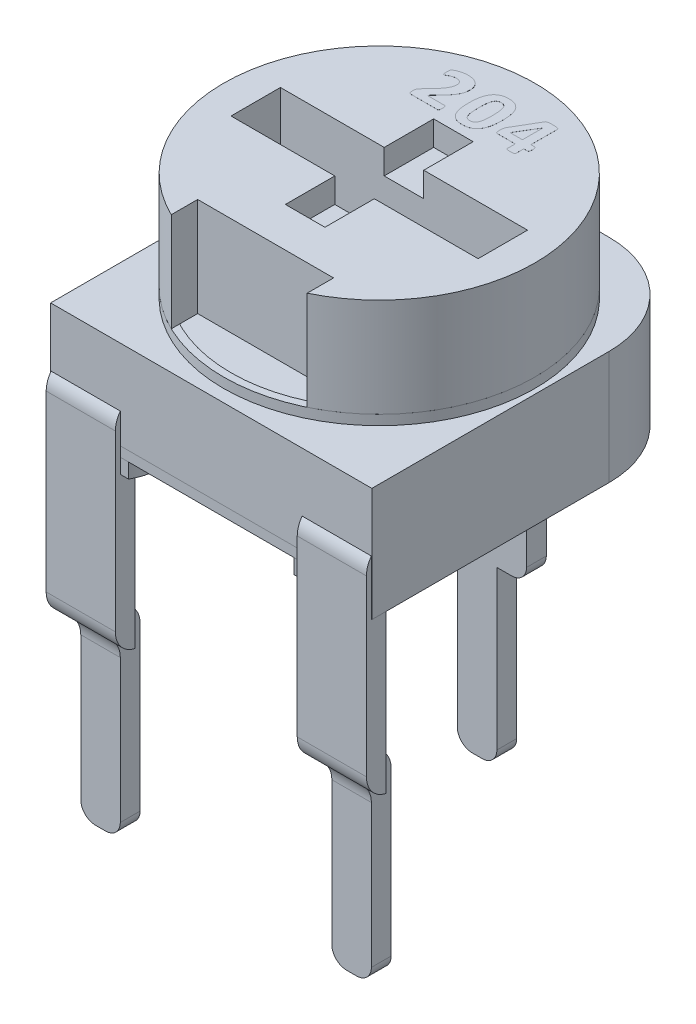
SolidWorks part; units mm, degrees
material "ABS"
ref_plane "Front Plane" through (0, 0, 0) normal (0, 0, 1) x (1, 0, 0)
ref_plane "Top Plane" through (0, 0, 0) normal (0, 1, 0) x (1, 0, 0)
ref_plane "Right Plane" through (0, 0, 0) normal (1, 0, 0) x (0, 0, -1)
sketch "Sketch1" plane through (0, 0, 0) normal (0, 1, 0) x (1, 0, 0)
  line L0 (0, 3.15) -> (0, -3.15) construction
  line L1 (0, 3.15) -> (0, 3.4) construction
  line L2 (0, -3.15) -> (0, -3.4) construction
  line L3 (-3.15, 0) -> (3.15, 0) construction
  line L4 (3.15, 0) -> (3.25, 0) construction
  line L5 (-3.15, 0) -> (-3.25, 0) construction
  line L6 (-3.25, -3.4) -> (3.25, -3.4)
  line L7 (-3.25, -3.4) -> (-3.25, 3.4)
  line L8 (-3.25, 3.4) -> (3.25, 3.4)
  line L9 (3.25, 3.4) -> (3.25, -3.4)
  circle A0 centre (0, 0) radius 3.15 construction
  dimension "D1" = 6.3
  dimension "D2" = 6.8
  dimension "D3" = 6.5
extrude "Boss-Extrude1" add sketch "Sketch1" along normal blind 2.3
sketch "Sketch2" plane through (0, 2.3, 0) normal (0, 1, 0) x (1, 0, 0)
  circle A0 centre (0, 0) radius 3.15 construction
  circle A1 centre (0, 0) radius 3.15
extrude "Boss-Extrude2" add sketch "Sketch2" along normal blind 0.2
fillet "Fillet1" radius 2 2 edges at (3.25, 1.15, -3.4) (-3.25, 1.15, -3.4)
sketch "Sketch3" plane through (0, 0, 0) normal (0, -1, 0) x (1, 0, 0)
  line L0 (0, 0) -> (0, -2.5) construction
  line L1 (-1.75, -2.5) -> (1.75, -2.5)
  line L6 (-2.25, -2) -> (-2.25, 2)
  line L7 (2.25, -2) -> (2.25, 2)
  line L8 (-2.25, 2) -> (-3, 2)
  line L9 (-3, 2) -> (-3, 3.4)
  line L10 (-3.25, 3.4) -> (3.25, 3.4) construction
  line L11 (2.25, 2) -> (3, 2)
  line L12 (3, 2) -> (3, 3.4)
  line L13 (3, 3.4) -> (-3, 3.4)
  line L14 (0, 0) -> (0, 3.4) construction
  arc A0 (-1.75, -2.5) -> (-2.25, -2) centre (-1.75, -2) cw
  arc A1 (1.75, -2.5) -> (2.25, -2) centre (1.75, -2) ccw
  point P20 (2.25, -2.5)
  dimension "D6" = 0.5
  dimension "D1" = 4.5
  dimension "D2" = 2.5
  dimension "D3" = 4.5
  dimension "D4" = 1.4
  dimension "D5" = 6
extrude "Cut-Extrude1" cut sketch "Sketch3" against normal blind 0.5
sketch "Sketch4" plane through (0, 0.5, 0) normal (0, -1, 0) x (1, 0, 0)
  line L8 (-3, 2) -> (-2.25, 2)
  line L9 (-2.25, 2) -> (-2.25, -2)
  line L10 (-1.75, -2.5) -> (1.75, -2.5)
  line L11 (2.25, -2) -> (2.25, 2)
  line L12 (2.25, 2) -> (3, 2)
  line L13 (3, 2) -> (3, 3.4)
  line L14 (3, 3.4) -> (-3, 3.4)
  line L15 (-3, 3.4) -> (-3, 2)
  line L16 (-3, 2) -> (-2.25, 2)
  line L17 (-2.25, 2) -> (-2.25, -2)
  line L18 (-1.75, -2.5) -> (1.75, -2.5)
  line L19 (2.25, -2) -> (2.25, 2)
  line L20 (2.25, 2) -> (3, 2)
  line L21 (3, 2) -> (3, 3.4)
  line L22 (3, 3.4) -> (-3, 3.4)
  line L23 (-3, 3.4) -> (-3, 2)
  arc A2 (-2.25, -2) -> (-1.75, -2.5) centre (-1.75, -2) ccw
  arc A3 (1.75, -2.5) -> (2.25, -2) centre (1.75, -2) ccw
  arc A4 (-2.25, -2) -> (-1.75, -2.5) centre (-1.75, -2) ccw
  arc A5 (1.75, -2.5) -> (2.25, -2) centre (1.75, -2) ccw
  dimension "D1" = 0
extrude "Boss-Extrude3" add sketch "Sketch4" along normal blind 0.2 separate body
sketch "Sketch5" plane through (0, 0.3, 0) normal (0, -1, 0) x (1, 0, 0)
  line L0 (0, 3.4) -> (0, 2.9) construction
  line L1 (3, 3.4) -> (-3, 3.4) construction
  line L2 (0, 2.9) -> (0, -2.18) construction
  line L3 (-2.54, 2.9) -> (2.54, 2.9) construction
  circle A0 centre (2.54, 2.9) radius 1
  circle A1 centre (-2.54, 2.9) radius 1
  circle A2 centre (0, -2.18) radius 1
  dimension "D2" = 5.08
  dimension "D4" = 2
  dimension "D1" = 0.5
  dimension "D3" = 5.08
extrude "Boss-Extrude4" add sketch "Sketch5" along normal up to surface (0.3 mm away) up to face at (0, 0, 0.1228)
sketch "Sketch6" plane through (0, 0.3, 0) normal (0, 1, 0) x (1, 0, 0)
  line L0 (-3.25, -3.4) -> (-3.25, -1)
  line L1 (-3.25, 1.4) -> (-3.25, -3.4) construction
  line L2 (-3.25, -1) -> (-4.35, -1)
  line L3 (-4.35, -1) -> (-4.35, -4.5)
  line L4 (-4.35, -4.5) -> (4.35, -4.5)
  line L5 (4.35, -4.5) -> (4.35, -1)
  line L6 (4.35, -1) -> (3.25, -1)
  line L7 (3.25, -3.4) -> (3.25, 1.4) construction
  line L8 (-3.25, -3.4) -> (3.25, -3.4)
  line L9 (3.25, -3.4) -> (3.25, -1)
  line L10 (0, 0) -> (0, -3.4) construction
  line L11 (0, -3.4) -> (0, -4.5) construction
  dimension "D1" = 3.5
extrude "Cut-Extrude2" cut sketch "Sketch6" against normal up to surface (0.3 mm away) up to face at (0, 0, -0.817)
sketch "Sketch8" plane through (0, 0.3, 0) normal (0, -1, 0) x (1, 0, 0)
  line L1 (-0.4, -1.98) -> (0.4, -1.98)
  line L2 (-0.4, -1.98) -> (-0.4, -2.38)
  line L3 (-0.4, -2.38) -> (0.4, -2.38)
  line L4 (0.4, -1.98) -> (0.4, -2.38)
  line L5 (-0.4, -1.98) -> (0.4, -2.38) construction
  line L6 (-0.4, -2.38) -> (0.4, -1.98) construction
  line L7 (-2.94, 3.1) -> (-2.14, 3.1)
  line L8 (-2.94, 3.1) -> (-2.94, 2.7)
  line L9 (-2.94, 2.7) -> (-2.14, 2.7)
  line L10 (-2.14, 3.1) -> (-2.14, 2.7)
  line L11 (-2.94, 3.1) -> (-2.14, 2.7) construction
  line L12 (-2.94, 2.7) -> (-2.14, 3.1) construction
  line L13 (2.94, 3.1) -> (2.14, 3.1)
  line L14 (2.94, 3.1) -> (2.94, 2.7)
  line L15 (2.94, 2.7) -> (2.14, 2.7)
  line L16 (2.14, 3.1) -> (2.14, 2.7)
  line L17 (2.94, 3.1) -> (2.14, 2.7) construction
  line L18 (2.94, 2.7) -> (2.14, 3.1) construction
  point P0 (0, -2.18)
  point P5 (-2.54, 2.9)
  point P11 (2.54, 2.9)
  dimension "D1" = 0.4
  dimension "D2" = 0.8
extrude "Boss-Extrude5" add sketch "Sketch8" along normal blind 7
sketch "Sketch9" plane through (0, 0.3, 0) normal (0, -1, 0) x (1, 0, 0)
  line L4 (0, -1.98) -> (0, -2.38) construction
  line L5 (0.4, -1.98) -> (-0.4, -1.98) construction
  line L6 (-0.4, -2.38) -> (0.4, -2.38) construction
  line L8 (-1, -1.98) -> (1, -1.98)
  line L9 (-1, -1.98) -> (-1, -2.38)
  line L10 (-1, -2.38) -> (1, -2.38)
  line L11 (1, -1.98) -> (1, -2.38)
  line L12 (-1, -1.98) -> (1, -2.38) construction
  line L13 (-1, -2.38) -> (1, -1.98) construction
  point P14 (0, -2.18)
  dimension "D1" = 2
extrude "Boss-Extrude6" add sketch "Sketch9" along normal blind 3.5
sketch "Sketch10" plane through (0, 0.3, 0) normal (0, -1, 0) x (1, 0, 0)
  line L0 (-2.54, 3.1) -> (-2.54, 3.5) construction
  line L1 (-2.14, 3.1) -> (-2.94, 3.1) construction
  line L2 (2.54, 3.1) -> (2.54, 3.5) construction
  line L3 (2.94, 3.1) -> (2.14, 3.1) construction
  line L4 (-2.94, 3.1) -> (-2.94, 2.7) construction
  line L5 (-3.24, 3.5) -> (-1.84, 3.5)
  line L6 (-3.24, 3.5) -> (-3.24, 3.1)
  line L7 (-3.24, 3.1) -> (-1.84, 3.1)
  line L8 (-1.84, 3.5) -> (-1.84, 3.1)
  line L10 (1.84, 3.5) -> (3.24, 3.5)
  line L11 (1.84, 3.5) -> (1.84, 3.1)
  line L12 (1.84, 3.1) -> (3.24, 3.1)
  line L13 (3.24, 3.5) -> (3.24, 3.1)
  dimension "D1" = 1.4
extrude "Boss-Extrude7" add sketch "Sketch10" along normal blind 3.5 and the other way blind 1
fillet "Fillet2" radius 0.5 2 edges at (2.54, 1.3, 3.5) (-2.54, 1.3, 3.5)
sketch "Sketch11" plane through (0, 0, 0) normal (1, 0, 0) x (0, 0, -1)
  line L0 (-3.4, 0) -> (1.4, 0) construction
  line L1 (-3.1, -2.8) -> (-2.7, -2.8)
  line L2 (-3.1, -2.8) -> (-3.1, 0)
  line L3 (-3.1, 0) -> (-2.7, 0)
  line L4 (-2.7, -2.8) -> (-2.7, 0)
  line L5 (-2.7, -6.7) -> (-2.7, 0.3) construction
  line L6 (-3.1, -2.8) -> (-3.1, -3.2) construction
extrude "Cut-Extrude3" cut sketch "Sketch11" against normal through all both and the other way through all
fillet "Fillet3" radius 0.5 4 edges at (-2.54, -2.8, 3.1) (2.54, -2.8, 3.1) (-2.54, -3.2, 3.5) (2.54, -3.2, 3.5)
fillet "Fillet4" radius 0.5 4 edges at (2.54, -2.8, 2.7) (-2.54, -2.8, 2.7) (2.54, -3.2, 3.1) (-2.54, -3.2, 3.1)
fillet "Fillet5" radius 0.3 12 edges at (-1, -3.2, -2.18) (1, -3.2, -2.18) (-0.4, -6.7, -2.18) (0.4, -6.7, -2.18) (2.14, -6.7, 2.9) (2.94, -6.7, 2.9) (-2.94, -6.7, 2.9) (-2.14, -6.7, 2.9) (-2.14, -2.7551, 3.1) (-2.94, -2.7551, 3.1) (2.14, -2.7551, 3.1) (2.94, -2.7551, 3.1)
sketch "Sketch12" plane through (0, 0.3, 0) normal (0, -1, 0) x (1, 0, 0)
  circle A0 centre (0, 0) radius 2
  circle A1 centre (0, 0) radius 1.5
  dimension "D1" = 4
  dimension "D2" = 3
extrude "Boss-Extrude8" add sketch "Sketch12" along normal blind 0.15
sketch "Sketch15" plane through (0, 2.5, 0) normal (0, 1, 0) x (1, 0, 0)
  circle A0 centre (0, 0) radius 3
  dimension "D1" = 6
extrude "Cut-Extrude4" cut sketch "Sketch15" against normal blind 0.5
sketch "Sketch14" plane through (0, 2.5, 0) normal (0, 1, 0) x (1, 0, 0)
  circle A1 centre (0, 0) radius 3.15
  circle A2 centre (0, 0) radius 3.15
  dimension "D1" = 0
extrude "Boss-Extrude9" add sketch "Sketch14" along normal blind 2 separate body
sketch "Set Angle of Knob" plane through (0, 4.5, 0) normal (0, 1, 0) x (1, 0, 0)
  line L0 (0, 0) -> (0, -3.15) construction
  line L1 (-2.5, 0) -> (2.5, 0) construction
  line L2 (-2.5, 0.5) -> (-2.5, -0.5)
  line L3 (2.5, 0.5) -> (2.5, -0.5)
  line L4 (-2.5, 0.5) -> (-0.4, 0.5)
  line L5 (-2.5, -0.5) -> (-0.4, -0.5)
  line L6 (0, 0) -> (0, -1.5) construction
  line L7 (0, 0) -> (0, 1.5) construction
  line L8 (0, 1.5) -> (0, 3.15) construction
  line L9 (0.4, 1.5) -> (-0.4, 1.5)
  line L10 (0.4, 1.5) -> (0.4, 0.5)
  line L11 (-0.4, 1.5) -> (-0.4, 0.5)
  line L12 (0.4, 0.5) -> (2.5, 0.5)
  line L13 (-0.4, -1.5) -> (0.4, -1.5)
  line L14 (-0.4, -1.5) -> (-0.4, -0.5)
  line L15 (0.4, -1.5) -> (0.4, -0.5)
  line L16 (0.4, -0.5) -> (2.5, -0.5)
  line L17 (0, -1.5) -> (0, -2.3) construction
  line L18 (-1.375, -2.3) -> (1.375, -2.3)
  line L19 (-1.375, -2.3) -> (-1.375, -3.8)
  line L20 (1.375, -2.3) -> (1.375, -3.8)
  line L21 (-1.375, -3.8) -> (1.375, -3.8)
  line L22 (-1, 0.25) -> (1, 0.25) construction
  line L23 (-1, 0.25) -> (-1, -0.25) construction
  line L24 (-1, -0.25) -> (1, -0.25) construction
  line L25 (1, -0.25) -> (1, 0.25) construction
  circle A0 centre (0, 0) radius 3.15 construction
  circle A1 centre (0, 0) radius 3.15 construction
  point P32 (0, 0.25)
  dimension "D1" = 1
  dimension "D2" = 0.8
  dimension "D3" = 1.5
  dimension "D4" = 5
  dimension "D5" = 90
  dimension "D6" = 2.75
  dimension "D7" = 1.5
  dimension "D8" = 1.8
  dimension "D9" = 0.25
  dimension "D10" = 0.25
  dimension "D11" = 2
extrude "TURN KNOB" cut sketch "Set Angle of Knob" against normal blind 2.3
sketch "Sketch17" plane through (0, 2, 0) normal (0, 1, 0) x (1, 0, 0)
  line L0 (-0.4, -1.5) -> (0.4, -1.5)
  line L1 (0.4, -1.5) -> (0.4, -0.5)
  line L2 (0.4, 1.5) -> (-0.4, 1.5)
  line L3 (-0.4, 1.5) -> (-0.4, 0.5)
  line L4 (-0.4, 0.5) -> (0.4, 0.5)
  line L5 (-0.4, -0.5) -> (0.4, -0.5)
  line L6 (-0.4, -0.5) -> (-0.4, -1.5)
  line L7 (0.4, 0.5) -> (0.4, 1.5)
extrude "Boss-Extrude10" add sketch "Sketch17" along normal blind 2
sketch "Sketch20" plane through (0, 2, 0) normal (0, 1, 0) x (1, 0, 0)
  line L0 (-1, 0.25) -> (1, 0.25) construction
  line L1 (-1, 0.25) -> (1, 0.25)
  line L2 (-1, -0.25) -> (1, -0.25) construction
  line L3 (-1, -0.25) -> (1, -0.25)
  line L4 (-1, 0.25) -> (-1, -0.25) construction
  line L5 (-1, 0.25) -> (-1, -0.25)
  line L6 (1, -0.25) -> (1, 0.25) construction
  line L7 (1, -0.25) -> (1, 0.25)
extrude "Cut-Extrude6" cut sketch "Sketch20" against normal blind 0.5
fillet "Fillet6" radius 0.2 2 edges at (1, 2, 0) (-1, 2, 0)
sketch "See Code in Properties" plane through (0, 4.5, 0) normal (0, 1, 0) x (1, 0, 0)
  line L0 (0, 1.5) -> (0, 1.7) construction
  line L1 (0.4, 1.5) -> (-0.4, 1.5) construction
  line L2 (0, 1.5) -> (0, 3.15) construction
  line L3 (-1.5, 1.7) -> (1.5, 1.7) construction
  text T0 "204" font "Calibri" height 0.9
  dimension "D1" = 0.2
  dimension "D2" = 3
extrude "Code Number" add sketch "See Code in Properties" along normal blind 0.001
